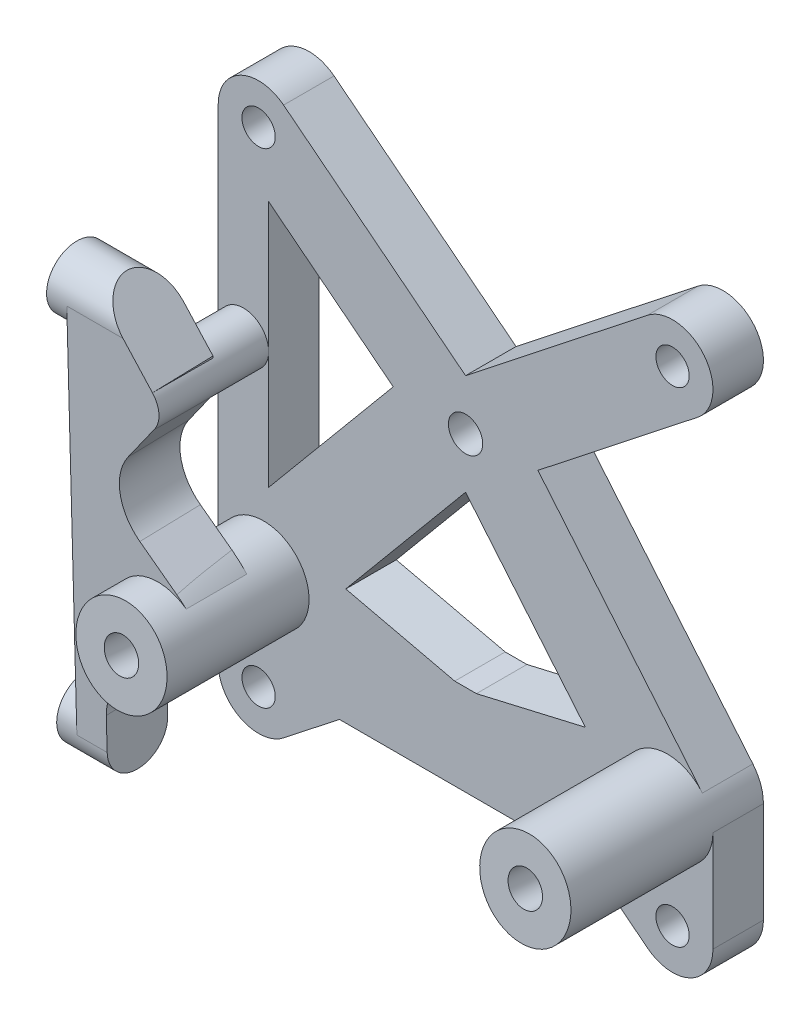
SolidWorks part; units mm, degrees
ref_plane "Ebene vorne" through (0, 0, 0) normal (0, 0, 1) x (1, 0, 0)
ref_plane "Ebene oben" through (0, 0, 0) normal (0, 1, 0) x (1, 0, 0)
ref_plane "Ebene rechts" through (0, 0, 0) normal (1, 0, 0) x (0, 0, -1)
sketch "Skizze1" plane through (0, 0, 0) normal (0, 0, 1) x (1, 0, 0)
  circle A0 centre (20.5, -20) radius 4
  circle A1 centre (-20.5, -20) radius 4
  arc A2 (18.025, -23.1423) -> (24.5, -20) centre (20.5, -20) ccw construction
  arc A3 (-24.5, -20) -> (-18.025, -23.1423) centre (-20.5, -20) ccw construction
extrude "Aufsatz-Linear austragen1" add sketch "Skizze1" along normal blind 5
sketch "Skizze2" plane through (0, 0, 0) normal (0, 0, 1) x (1, 0, 0)
  line L0 (-12.5, -18.7907) -> (12.5, -18.7907) construction
  line L1 (-12.5, -18.7907) -> (12.5, -18.7907)
  line L2 (12.5, -18.7907) -> (18.025, -23.1423)
  line L3 (18.025, -23.1423) -> (22.975, -16.8577)
  line L4 (22.975, -16.8577) -> (14.0026, -9.7907)
  line L5 (14.0026, -9.7907) -> (-14.0026, -9.7907)
  line L6 (0, -20.6718) -> (0, 16.0303) construction
  line L8 (0, -9.7907) -> (0, -18.7907) construction
  line L9 (-22.975, -16.8577) -> (-14.0026, -9.7907)
  line L10 (-18.025, -23.1423) -> (-22.975, -16.8577)
  line L11 (-12.5, -18.7907) -> (-18.025, -23.1423)
  circle A1 centre (20.5, -20) radius 4 construction
  dimension "D1" = 9
extrude "Aufsatz-Linear austragen3" add sketch "Skizze2" along normal through all
sketch "Skizze3" plane through (0, 0, 0) normal (0, 0, 1) x (1, 0, 0)
  line L0 (0, -7.529) -> (0, -14.5334) construction
  line L1 (0, -20.6718) -> (0, 16.0303) construction
  line L2 (-24.5, 28) -> (-24.5, -20) construction
  circle A0 centre (-20, -10.0125) radius 4.5
  circle A1 centre (20, -10.0125) radius 4.5
  circle A2 centre (-20.5, -20) radius 1.65 construction
  dimension "D1" = 9
  dimension "D2" = 10
extrude "Aufsatz-Linear austragen4" add sketch "Skizze3" along normal up to surface (19.0834 mm away)
sketch "Skizze4" plane through (0, 0, 0) normal (0, 0, -1) x (-1, 0, 0)
  line L0 (-18.9815, -5.6293) -> (-1.0733, -9.7907)
  line L1 (-14.0026, -9.7907) -> (14.0026, -9.7907) construction
  line L2 (-1.0733, -9.7907) -> (-18.025, -23.1423)
  line L3 (-18.025, -23.1423) -> (-24.5, -20)
  line L4 (-24.5, -20) -> (-24.5, -10.0125)
  line L5 (-24.5, -10.0125) -> (-18.9815, -5.6293)
  line L6 (-12.5, -18.7907) -> (-18.025, -23.1423) construction
  line L7 (0, 0) -> (0, -5.6293) construction
  line L8 (24.5, -10.0125) -> (18.9815, -5.6293)
  line L9 (24.5, -20) -> (24.5, -10.0125)
  line L10 (18.025, -23.1423) -> (24.5, -20)
  line L11 (1.0733, -9.7907) -> (18.025, -23.1423)
  line L12 (18.9815, -5.6293) -> (1.0733, -9.7907)
  arc A0 (-15.6258, -11.0692) -> (-19.9975, -14.5125) centre (-20, -10.0125) ccw construction
  arc A1 (-22.975, -16.8577) -> (-18.025, -23.1423) centre (-20.5, -20) ccw construction
extrude "Aufsatz-Linear austragen5" add sketch "Skizze4" against normal up to surface (5 mm away) up to face at (0, -16.2325, 5)
sketch "Skizze5" plane through (0, 0, 0) normal (0, 0, 1) x (1, 0, 0)
  line L2 (18.025, 31.1423) -> (0, 16.9453)
  line L3 (0, -20.6718) -> (0, 16.0303) construction
  line L4 (0, 16.9453) -> (-18.025, 31.1423)
  line L14 (12.5, 26.7907) -> (18.025, 31.1423) construction
  line L15 (-22.975, 24.8577) -> (-7.1654, 12.4055)
  line L17 (22.975, 24.8577) -> (7.1654, 12.4055)
  line L18 (7.1654, 12.4055) -> (23.4561, -7.1306)
  line L19 (23.4561, -7.1306) -> (16.5439, -12.8944)
  line L20 (16.5439, -12.8944) -> (0, 6.9453)
  line L21 (0, -1.3658) -> (0, -17.2293) construction
  line L22 (-16.5439, -12.8944) -> (0, 6.9453)
  line L23 (-23.4561, -7.1306) -> (-16.5439, -12.8944)
  line L24 (-7.1654, 12.4055) -> (-23.4561, -7.1306)
  arc A0 (-22.975, 24.8577) -> (-18.025, 31.1423) centre (-20.5, 28) cw
  arc A1 (-18.025, 31.1423) -> (-24.5, 28) centre (-20.5, 28) ccw construction
  arc A2 (22.975, 24.8577) -> (18.025, 31.1423) centre (20.5, 28) ccw
  arc A3 (24.5, 28) -> (18.025, 31.1423) centre (20.5, 28) ccw construction
  circle A6 centre (20, -10.0125) radius 4.5 construction
  dimension "D1" = 10
extrude "Aufsatz-Linear austragen6" add sketch "Skizze5" along normal up to surface (5 mm away) up to face at (0, -15.8514, 5)
sketch "Skizze11" plane through (-30.5, 0, 0) normal (1, 0, 0) x (0, 0, -1)
  line L0 (-18.1767, -4.5522) -> (-9.8217, -4.3282) construction
  circle A0 centre (-12, -23.05) radius 3
  circle A1 centre (-13, 14.25) radius 3
  dimension "D1" = 6
extrude "Aufsatz-Linear austragen7" add sketch "Skizze11" along normal blind 5 separate body
sketch "Skizze12" plane through (-30.5, 0, 0) normal (-1, 0, 0) x (0, 0, 1)
  line L0 (10.0011, 14.3304) -> (9.0011, -22.9696)
  line L1 (9.0011, -22.9696) -> (14.9989, -23.1304)
  line L2 (14.9989, -23.1304) -> (15.9989, 14.1696)
  line L3 (15.9989, 14.1696) -> (10.0011, 14.3304)
  circle A0 centre (13, 14.25) radius 3 construction
  circle A1 centre (12, -23.05) radius 3 construction
extrude "Aufsatz-Linear austragen8" add sketch "Skizze12" along normal blind 3 from surface at -5 starting at face at (-25.5, -20.05, 12)
sketch "Skizze13" plane through (0, -0.4184, 15.6078) normal (0, -0.0268, 0.9996) x (1, 0, 0)
  line L0 (-25.5, 0.5025) -> (-17.2244, -5.965)
  line L1 (-25.5, 14.5933) -> (-25.5, -22.7201) construction
  line L2 (-25.5, -19.4975) -> (-17.2244, -13.0299)
  line L3 (-25.5, 0.5025) -> (-25.5, -19.4975)
  line L4 (-17.2244, -5.965) -> (-17.2244, -13.0299)
  line L5 (-25.5, -9.4975) -> (-17.2244, -9.4975) construction
  ellipse E0 centre (-20, -9.4975) end of major axis (-24.5, -9.4975) minor radius 4.4878 construction
  dimension "D1" = 20
extrude "Aufsatz-Linear austragen9" add sketch "Skizze13" against normal up to surface (6 mm away) up to face at (-27, -4.3196, 9.5011)
fillet "Verrundung1" radius 10 1 edges at (-17.2244, -6.3009, 12.449)
sketch "Skizze14" plane through (0, 0, 5) normal (0, 0, 1) x (1, 0, 0)
  line L1 (-24.5, 28) -> (-19.5, 28)
  line L2 (-24.5, 28) -> (-24.5, -14.4846)
  line L3 (-24.5, -14.4846) -> (-19.5, -14.4846)
  line L4 (-19.5, 28) -> (-19.5, -14.4846)
  arc A0 (-18.025, 31.1423) -> (-22.975, 24.8577) centre (-20.5, 28) ccw construction
  circle A1 centre (-20, -10.0125) radius 4.5 construction
  arc A2 (-24.5, -10.0125) -> (-23.4561, -7.1306) centre (-20, -10.0125) ccw construction
  dimension "D1" = 5
extrude "Aufsatz-Linear austragen10" add sketch "Skizze14" against normal up to surface (5 mm away) up to face at (0, -0.1951, 0)
sketch "Skizze15" plane through (0, 0, 5) normal (0, 0, 1) x (1, 0, 0)
  line L0 (-19.5, -2.3864) -> (-19.5, 22.1206) construction
  line L2 (-24.5, 28) -> (-24.5, -10.0125) construction
  line L3 (-22, 9.25) -> (-16.7663, 9.25) construction
  line L6 (-25.5, 17.25) -> (-30.5, 17.25) construction
  circle A0 centre (-22, 9.25) radius 2.5
  dimension "D1" = 8
extrude "Aufsatz-Linear austragen11" add sketch "Skizze15" along normal up to surface (10.867 mm away)
sketch "Skizze16" plane through (0, -0.4184, 15.6078) normal (0, -0.0268, 0.9996) x (1, 0, 0)
  line L0 (-25.5, 17.5933) -> (-20.1027, 11.3004)
  line L1 (-20.1027, 11.3004) -> (-19.9688, 8.2139)
  line L2 (-19.9688, 8.2139) -> (-25.5, 0.5025)
  line L3 (-25.5, 14.5933) -> (-25.5, 0.5025) construction
  line L4 (-25.5, 0.5025) -> (-25.5, 17.5933)
  line L5 (-18.1255, -5.2608) -> (-25.5, 0.5025) construction
  ellipse E0 centre (-22, 9.6719) end of major axis (-22, 7.171) minor radius 2.5 construction
extrude "Aufsatz-Linear austragen12" add sketch "Skizze16" against normal up to surface (6 mm away) up to face at (-24.5183, -6.7618, 9.4356)
sketch "Skizze18" plane through (-30.5, 0, 0) normal (-1, 0, 0) x (0, 0, 1)
  line L0 (10.0011, 14.3304) -> (10.2214, 22.548)
  line L1 (10.2214, 22.548) -> (16.2192, 22.3872)
  line L2 (16.2192, 22.3872) -> (15.9989, 14.1696)
  line L3 (15.9989, 14.1696) -> (14.9989, -23.1304) construction
  arc A0 (10.0011, 14.3304) -> (15.9989, 14.1696) centre (13, 14.25) cw
  circle A1 centre (13, 14.25) radius 3 construction
extrude "Schnitt-Linear austragen4" cut sketch "Skizze18" against normal through all
fillet "Verrundung2" radius 5 1 edges at (-25.5, 0.1643, 12.6224)
sketch "Skizze10" plane through (0, 0, 5) normal (0, 0, 1) x (1, 0, 0)
  line L0 (0, 28) -> (0, 4) construction
  line L1 (0, 4) -> (29.8326, 4) construction
  circle A0 centre (-20.5, 28) radius 1.65
  circle A1 centre (20.5, 28) radius 1.65
  circle A2 centre (20.5, -20) radius 1.65
  circle A3 centre (-20.5, -20) radius 1.65
  dimension "D1" = 3.3
extrude "Schnitt-Linear austragen2" cut sketch "Skizze10" against normal through all
sketch "Skizze9" plane through (0, 1.5808, 18.0692) normal (0, 0.0872, 0.9962) x (1, 0, 0)
  line L0 (0, -3.2637) -> (0, -25.4568) construction
  circle A0 centre (20, -11.6376) radius 1.7
  circle A1 centre (-20, -11.6376) radius 1.7
  ellipse E0 centre (-20, -11.6376) end of major axis (-20, -16.1548) minor radius 4.5 construction
  dimension "D1" = 3.4
extrude "Schnitt-Linear austragen1" cut sketch "Skizze9" against normal blind 4
sketch "Skizze19" plane through (-30.5, 0, 0) normal (-1, 0, 0) x (0, 0, 1)
  line L0 (8.9658, -4.3052) -> (18.1107, -4.5504) construction
  circle A0 centre (13, 14.25) radius 1.7
  circle A1 centre (13, 14.25) radius 3 construction
  circle A2 centre (12, -23.05) radius 1.7
  circle A3 centre (12, -23.05) radius 3 construction
  dimension "D1" = 3.4
extrude "Schnitt-Linear austragen5" cut sketch "Skizze19" against normal blind 4
sketch "Skizze20" plane through (0, 0, 10) normal (0, 0, 1) x (1, 0, 0)
  line L1 (-25.5, -19.9089) -> (-25.5, -23.1304) construction
  circle A0 centre (-20.5, -20) radius 5
  arc A1 (-21.1927, -16.0604) -> (-19.8073, -23.9396) centre (-20.5, -20) ccw construction
extrude "Schnitt-Linear austragen6" cut sketch "Skizze20" along normal through all and the other way up to surface other way up to face at (-22.15, -20, 5)
sketch "Skizze21" plane through (0, 0, 5) normal (0, 0, 1) x (1, 0, 0)
  circle A0 centre (0, 11.9453) radius 1.7
  dimension "D1" = 3.4
extrude "Schnitt-Linear austragen7" cut sketch "Skizze21" against normal blind 4
equation "\"M2EinschmelzGewindeDurchmesser\"=3.4"
equation "\"M2EinschmelzGewindeTiefe\"= 4.0"
equation "\"M3EinschmelzGewindeDurchmesser\"= 4.2"
equation "\"M3EinschmelzGewindeTief\"= 5.7"
equation "\"M2SchraubeLoch\"=2.3"
equation "\"M3SchraubeLoch\"=3.3"
equation "\"offSetVonGummiReifen\"= 3.0"
equation "\"D1@Skizze9\"=\"M2EinschmelzGewindeDurchmesser\""
equation "\"D1@Schnitt-Linear austragen1\"=\"M2EinschmelzGewindeTiefe\""
equation "\"D1@Skizze19\"=\"M2EinschmelzGewindeDurchmesser\""
equation "\"D1@Schnitt-Linear austragen5\"=\"M2EinschmelzGewindeTiefe\""
equation "\"D1@Skizze21\"=\"M2EinschmelzGewindeDurchmesser\""
equation "\"D1@Schnitt-Linear austragen7\"=\"M2EinschmelzGewindeTiefe\""
